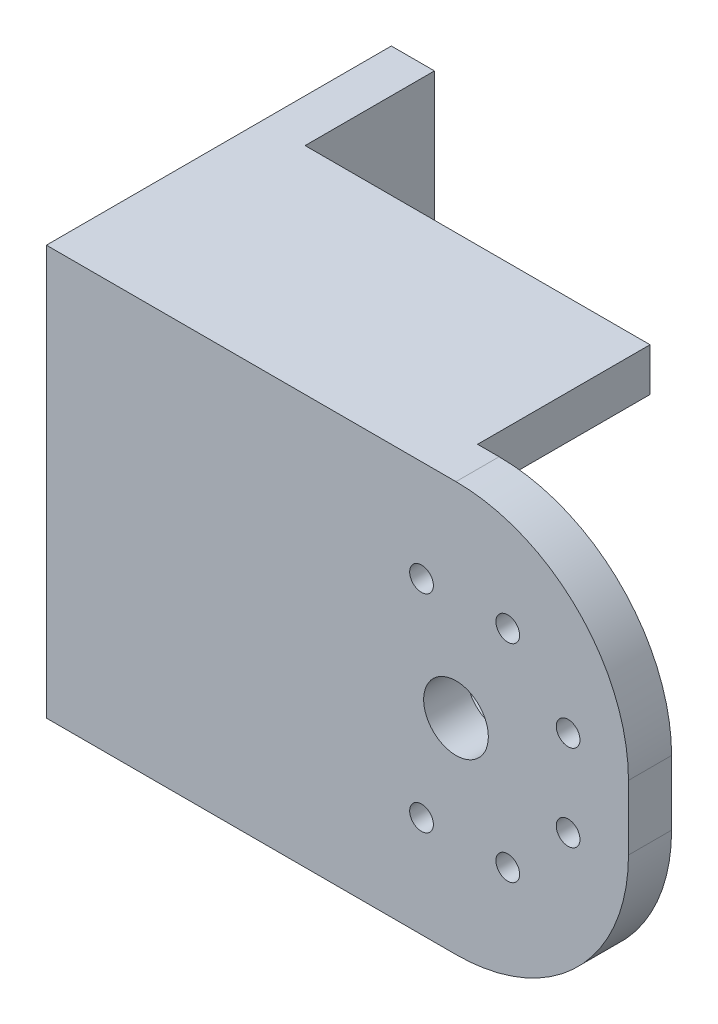
SolidWorks part; units mm, degrees
ref_plane "Front Plane" through (0, 0, 0) normal (0, 0, 1) x (1, 0, 0)
ref_plane "Top Plane" through (0, 0, 0) normal (0, 1, 0) x (1, 0, 0)
ref_plane "Right Plane" through (0, 0, 0) normal (1, 0, 0) x (0, 0, -1)
sketch "Sketch3" plane through (0, 0, 0) normal (0, 0, 1) x (1, 0, 0)
  line L6 (68.6171, 80.0599) -> (163.6171, 80.0599)
  line L10 (68.6171, 80.0599) -> (68.6171, -14.9401)
  line L36 (-101.4371, 49.8561) -> (-17.2351, 49.8561) construction
  line L70 (68.6171, -14.9401) -> (163.6171, -14.9401)
  line L71 (203.6171, 40.0599) -> (203.6171, 25.0599)
  circle A22 centre (163.6171, 32.5599) radius 7.5
  circle A23 centre (189.6171, 42.5599) radius 2.75
  circle A24 centre (155.6171, 56.5599) radius 2.75
  circle A25 centre (175.6171, 56.5599) radius 2.75
  circle A26 centre (155.6171, 8.5599) radius 2.75
  circle A27 centre (175.6171, 8.5599) radius 2.75
  circle A28 centre (189.6171, 22.5599) radius 2.75
  arc A29 (163.6171, -14.9401) -> (203.6171, 25.0599) centre (163.6171, 25.0599) ccw
  arc A30 (163.6171, 80.0599) -> (203.6171, 40.0599) centre (163.6171, 40.0599) cw
  point P23 (203.6171, 80.0599)
  dimension "D2" = 5.5
  dimension "D3" = 10
  dimension "D4" = 26
  dimension "D7" = 5.5
  dimension "D21" = 135
  dimension "D22" = 40
  dimension "D23" = 47.5
  dimension "D1" = 15
  dimension "D5" = 5.5
  dimension "D6" = 5.5
  dimension "D8" = 5.5
  dimension "D9" = 5.5
  dimension "D24" = 40
  dimension "D10" = 8
  dimension "D11" = 24
  dimension "D12" = 20
  dimension "D15" = 20
  dimension "D16" = 8
  dimension "D17" = 20
  dimension "D18" = 48
  dimension "D19" = 48
  dimension "D20" = 95
  dimension "D13" = 26
  dimension "D14" = 24
extrude "Boss-Extrude1" add sketch "Sketch3" along normal blind 10
sketch "Sketch4" plane through (0, 0, 0) normal (0, 0, -1) x (-1, 0, 0)
  line L0 (-68.6171, -14.9401) -> (-163.6171, -14.9401) construction
  line L1 (-68.6171, 80.0599) -> (-78.6171, 80.0599)
  line L2 (-68.6171, 80.0599) -> (-68.6171, -14.9401)
  line L3 (-68.6171, -14.9401) -> (-78.6171, -14.9401)
  line L4 (-78.6171, 80.0599) -> (-78.6171, -14.9401)
  dimension "D1" = 10
extrude "Boss-Extrude2" add sketch "Sketch4" along normal blind 70
sketch "Sketch5" plane through (0, 0, 0) normal (0, 0, -1) x (-1, 0, 0)
  line L1 (-78.6171, 80.0599) -> (-158.6171, 80.0599)
  line L2 (-78.6171, 80.0599) -> (-78.6171, 70.0599)
  line L3 (-78.6171, 70.0599) -> (-158.6171, 70.0599)
  line L4 (-158.6171, 80.0599) -> (-158.6171, 70.0599)
  line L5 (-78.6171, -14.9401) -> (-158.6171, -14.9401)
  line L6 (-78.6171, -14.9401) -> (-78.6171, -4.9401)
  line L7 (-78.6171, -4.9401) -> (-158.6171, -4.9401)
  line L8 (-158.6171, -14.9401) -> (-158.6171, -4.9401)
  dimension "D1" = 10
  dimension "D2" = 10
  dimension "D3" = 80
  dimension "D4" = 80
extrude "Boss-Extrude3" add sketch "Sketch5" along normal blind 40
sketch "Sketch6" plane through (0, -14.9401, 0) normal (0, -1, 0) x (1, 0, 0)
  line L0 (55, 0) -> (-55, 0) construction
  line L1 (88.6171, 0) -> (120.6171, 0)
  line L2 (88.6171, 0) -> (88.6171, -36)
  line L3 (88.6171, -36) -> (120.6171, -36)
  line L4 (120.6171, 0) -> (120.6171, -36)
  line L5 (68.6171, 10) -> (68.6171, -70) construction
  dimension "D1" = 20
  dimension "D2" = 36
  dimension "D3" = 32
extrude "Cut-Extrude1" cut sketch "Sketch6" against normal blind 43.8
fillet "Fillet2" [suppressed] radius 15
sketch "Sketch8" plane through (68.6171, 0, 0) normal (-1, 0, 0) x (0, 0, 1)
  line L0 (10, 80.0599) -> (-70, 80.0599) construction
  line L1 (-40, 32.5599) -> (-56.1679, 25.863) construction
  line L2 (-70, 32.5599) -> (0, 32.5599) construction
  line L3 (-70, -14.9401) -> (-70, 80.0599) construction
  circle A0 centre (-40, 32.5599) radius 7.5
  circle A1 centre (-56.1679, 25.863) radius 2.75
  circle A2 centre (-56.1679, 39.2569) radius 2.75
  circle A3 centre (-46.697, 48.7278) radius 2.75
  circle A4 centre (-33.303, 48.7278) radius 2.75
  circle A5 centre (-23.8321, 39.2569) radius 2.75
  circle A6 centre (-23.8321, 25.863) radius 2.75
  circle A7 centre (-33.303, 16.392) radius 2.75
  circle A8 centre (-46.697, 16.392) radius 2.75
  point P27 (-40, 32.5599)
  dimension "D1" = 15
  dimension "D6" = 5.5
  dimension "D2" = 47.5
  dimension "D3" = 30
  dimension "D4" = 17.5
  dimension "D5" = 22.5
  dimension "D7" = 8
extrude "Cut-Extrude2" cut sketch "Sketch8" against normal blind 43.8
fillet "Fillet3" radius 3 5 edges at (120.6171, -4.9401, -18) (120.6171, -14.9401, -18) (88.6171, -14.9401, -18) (88.6171, -4.9401, -18) (104.6171, -14.9401, 0)
